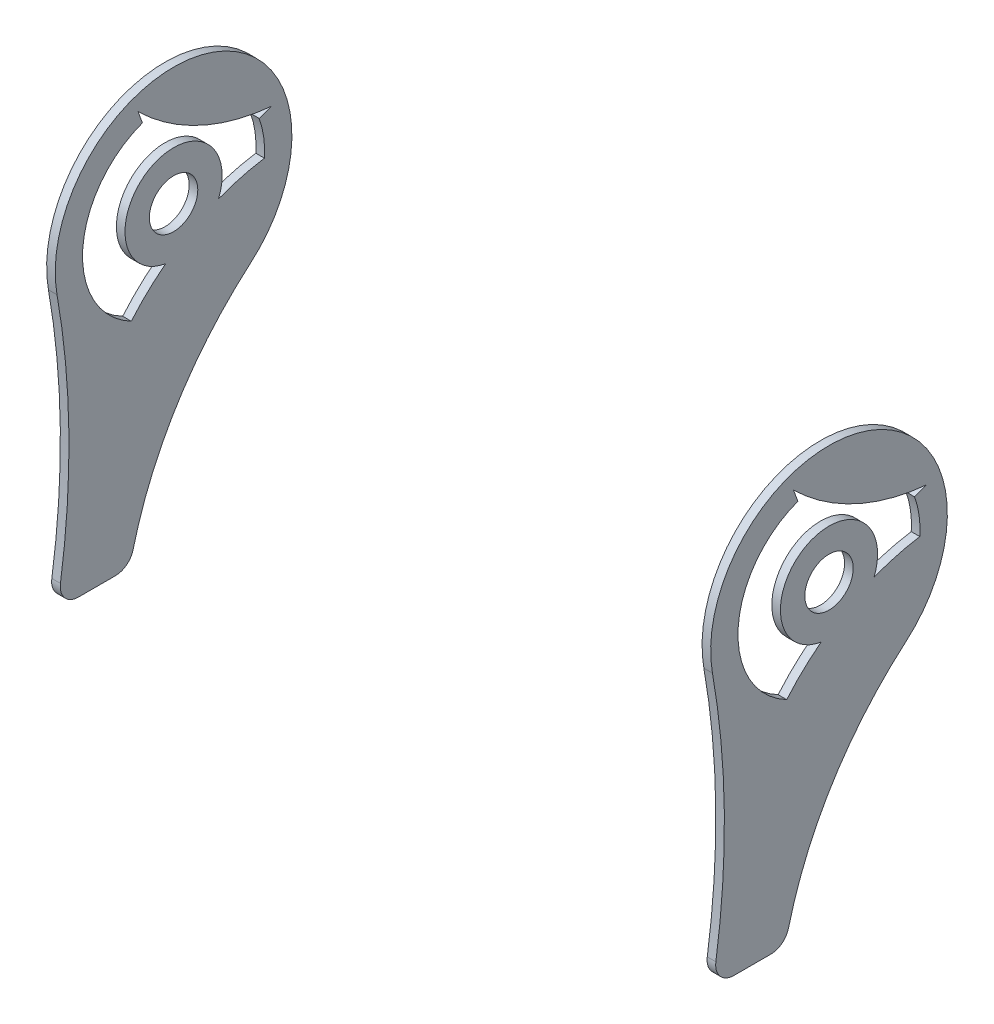
SolidWorks part; units mm, degrees
material "Ti-6Al-4VSolution treated and aged (SS)"
ref_plane "Front Plane" through (0, 0, 0) normal (0, 0, 1) x (1, 0, 0)
ref_plane "Top Plane" through (0, 0, 0) normal (0, 1, 0) x (1, 0, 0)
ref_plane "Right Plane" through (0, 0, 0) normal (1, 0, 0) x (0, 0, -1)
sketch "Sketch1" plane through (56.4, 0, 0) normal (1, 0, 0) x (0, 0, -1)
  line L0 (-195.72, -24.13) -> (-183.02, -24.13)
  line L1 (-195.72, -24.13) -> (-132.2785, -35.3164) construction
  arc A0 (-161.9774, 11.3114) -> (-195.7234, 23.4009) centre (-175.4, 26.9875) ccw
  arc A1 (-194.0448, 35.8349) -> (-195.7234, 23.4009) centre (-175.4, 26.9875) ccw construction
  circle A2 centre (-175.4, 26.9875) radius 4.2228
  arc A3 (-195.7234, 23.4009) -> (-195.72, -24.13) centre (-330.4451, -0.3743) cw
  arc A4 (-195.72, -24.13) -> (-195.7234, 23.4009) centre (-330.4451, -0.3743) ccw construction
  arc A5 (-183.02, -24.13) -> (-161.9774, 11.3114) centre (-120.2344, -37.4401) cw
  point P19 (0, 0)
  point P20 (0, 0)
  dimension "D1" = 8.4455
extrude "Boss-Extrude1" add sketch "Sketch1" along normal blind 1.5
sketch "Sketch2" plane through (57.9, 0, 0) normal (1, 0, 0) x (0, 0, -1)
  line L0 (-181.5897, 43.9936) -> (-180.8296, 41.9051)
  line L1 (-158.3939, 33.1772) -> (-160.4824, 32.4171)
  line L4 (-175.4, 26.9875) -> (-175.4, 53.9132) construction
  arc A0 (-167.5492, 23.7969) -> (-176.7707, 18.6247) centre (-175.4, 26.9875) ccw
  arc A1 (-180.8296, 41.9051) -> (-160.4824, 32.4171) centre (-175.4, 26.9875) ccw
  arc A2 (-161.9774, 11.3114) -> (-195.7234, 23.4009) centre (-175.4, 26.9875) ccw construction
  arc A3 (-181.5897, 43.9936) -> (-158.3939, 33.1772) centre (-154.8255, 71.1097) ccw
  arc A4 (-182.7735, 12.9288) -> (-176.7707, 18.6247) centre (-153.7022, -11.6978) cw
  arc A5 (-176.3864, 42.8318) -> (-162.6285, 36.4164) centre (-175.4, 26.9875) cw construction
  arc A6 (-176.3864, 42.8318) -> (-162.6285, 36.4164) centre (-154.8255, 71.1097) ccw construction
  circle A7 centre (-175.4, 26.9875) radius 18.0975 construction
  circle A8 centre (-175.4, 26.9875) radius 6.2548 construction
  circle A9 centre (-175.4, 26.9875) radius 4.2228 construction
  arc A10 (-167.5492, 23.7969) -> (-159.559, 25.9494) centre (-153.7022, -11.6978) cw
  point P21 (-167.8378, 23.5968)
  point P23 (-176.3864, 19.0073)
  point P24 (-176.3864, 18.8039)
  point P25 (-167.5492, 23.7969)
  dimension "D1" = 4.7625
  dimension "D2" = 2.54
  dimension "D3" = 2.54
  dimension "D5" = 38.1
  dimension "D6" = 38.1
  dimension "D7" = 2.032
  dimension "D4" = 20
extrude "Cut-Extrude1" cut sketch "Sketch2" against normal up to next and the other way through all contours A0 A10 A1 L1 A3 L0 A4 region at (57.9, 36.1694, 171.1184)
fillet "Fillet1" radius 3.175 2 edges at (57.15, -24.13, 183.02) (57.15, -24.13, 195.72)
mirror "Mirror2" about plane through (0, 0, 0) normal (1, 0, 0) of bodies 103 101
equation "\"weapon shaft threads\"= 5 / 16"
equation "\"D1@Sketch1\"=\"weapon shaft threads\" + .02in"
equation "\"D1@Boss-Extrude1\"=1.5mm"
